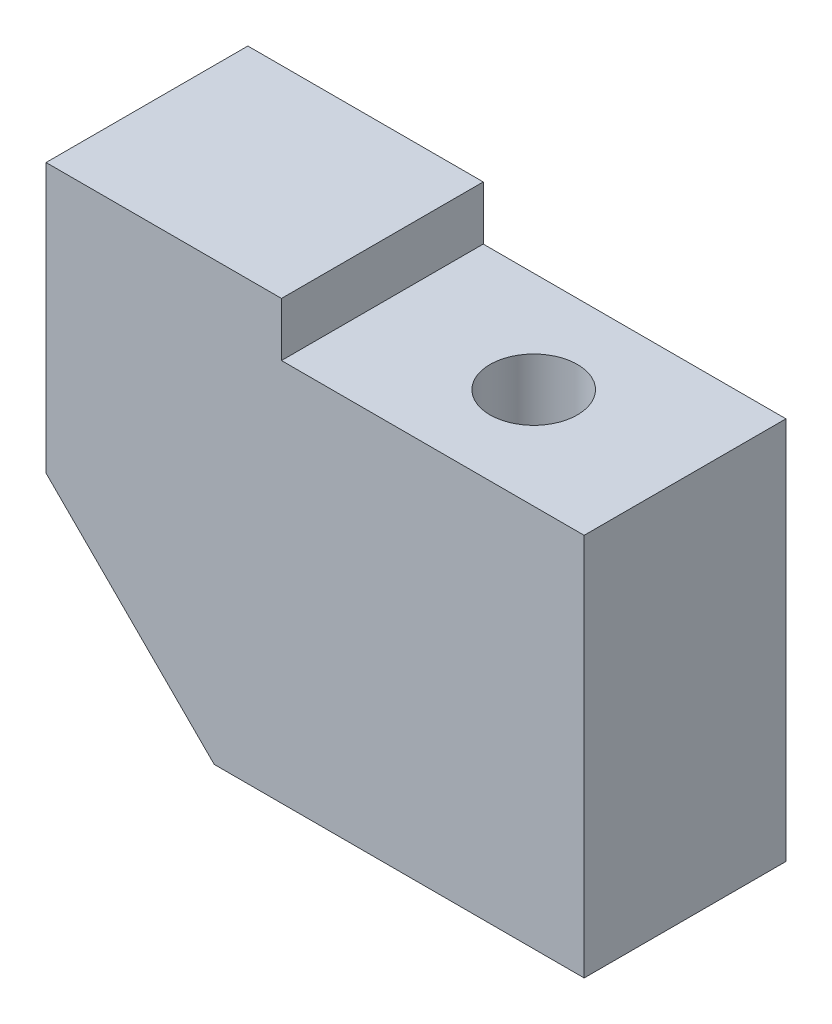
SolidWorks part; units mm, degrees
material "ABS"
ref_plane "Front Plane" through (0, 0, 0) normal (0, 0, 1) x (1, 0, 0)
ref_plane "Top Plane" through (0, 0, 0) normal (0, 1, 0) x (1, 0, 0)
ref_plane "Right Plane" through (0, 0, 0) normal (1, 0, 0) x (0, 0, -1)
sketch "Sketch1" plane through (0, 0, 0) normal (0, 0, 1) x (1, 0, 0)
  line L7 (-9.0352, 7.8649) -> (-2.0352, 7.8649)
  line L8 (6.9648, 6.2649) -> (6.9648, -5.1351)
  line L9 (-9.0352, 7.8649) -> (-9.0352, -0.1351)
  line L10 (-4.0352, -5.1351) -> (6.9648, -5.1351)
  line L11 (-9.0352, -0.1351) -> (-4.0352, -5.1351)
  line L12 (-2.0352, 7.8649) -> (-2.0352, 6.2649)
  line L13 (-2.0352, 6.2649) -> (6.9648, 6.2649)
extrude "Boss-Extrude1" add sketch "Sketch1" along normal blind 6
sketch "Sketch2" plane through (-9.0352, 0, 0) normal (-1, 0, 0) x (0, 0, 1)
  circle A0 centre (3, 3.8649) radius 1.5
extrude "Cut-Extrude1" cut sketch "Sketch2" against normal blind 9
sketch "Sketch3" plane through (0, 7.8649, 0) normal (0, 1, 0) x (1, 0, 0)
  circle A0 centre (2.4648, -3) radius 1.3
extrude "Cut-Extrude2" cut sketch "Sketch3" against normal through all
